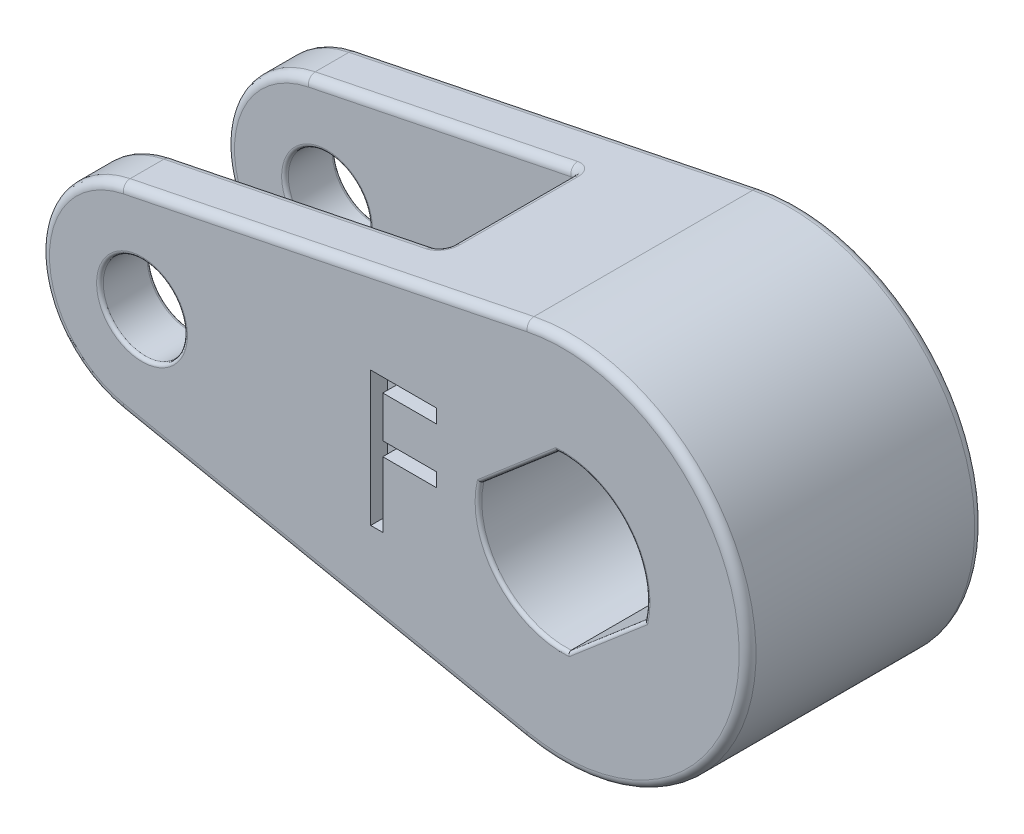
SolidWorks part; units mm, degrees
ref_plane "Front Plane" through (0, 0, 0) normal (0, 0, 1) x (1, 0, 0)
ref_plane "Top Plane" through (0, 0, 0) normal (0, 1, 0) x (1, 0, 0)
ref_plane "Right Plane" through (0, 0, 0) normal (1, 0, 0) x (0, 0, -1)
sketch "Sketch1" plane through (0, 0, 0) normal (0, 0, 1) x (1, 0, 0)
  line L0 (55, 0) -> (-55, 0) construction
  line L1 (-26.2, 5.8788) -> (-2.2, 10.7778)
  line L2 (-2.2, -10.7778) -> (-26.2, -5.8788)
  arc A0 (-2.2, 10.7778) -> (-2.2, -10.7778) centre (0, 0) cw
  arc A1 (-26.2, 5.8788) -> (-26.2, -5.8788) centre (-25, 0) ccw
  dimension "D1" = 11
  dimension "D2" = 6
  dimension "D3" = 25
extrude "Extrude1" add sketch "Sketch1" along normal blind 14
sketch "Sketch2" plane through (0, 0, 14) normal (0, 0, 1) x (1, 0, 0)
  line L0 (7.7, 0) -> (-7.7, 0) construction
  line L1 (-4.879, 1.0933) -> (-0.3166, 4.99)
  line L2 (4.879, -1.0933) -> (0.3166, -4.99)
  line L3 (0, 0) -> (-25, 0) construction
  arc A0 (-0.3166, 4.99) -> (4.879, -1.0933) centre (0, 0) cw
  circle A1 centre (-25, 0) radius 2.5
  arc A2 (-4.879, 1.0933) -> (0.3166, -4.99) centre (0, 0) ccw
  arc A4 (-26.2, 5.8788) -> (-26.2, -5.8788) centre (-25, 0) ccw construction
  dimension "D1" = 5
  dimension "D2" = 5
  dimension "D3" = 8
  dimension "D4" = 40.5
extrude "Cut-Extrude1" cut sketch "Sketch2" against normal through all
sketch "Sketch6" plane through (0, 0, 0) normal (1, 0, 0) x (0, 0, -1)
  line L1 (-11, 13) -> (-3, 13)
  line L2 (-11, 13) -> (-11, -13)
  line L3 (-11, -13) -> (-3, -13)
  line L4 (-3, 13) -> (-3, -13)
  dimension "D1" = 8
  dimension "D2" = 3
  dimension "D3" = 13
  dimension "D4" = 13
extrude "Cut-Extrude3" cut sketch "Sketch6" against normal through all from offset 10
ref_plane "Plane1" through (0, 0, 7) normal (0, 0, 1) x (1, 0, 0)
sketch "Sketch5" plane through (0, 0, 14) normal (0, 0, 1) x (1, 0, 0)
  line L0 (-25, 0) -> (0, 0) construction
  circle A0 centre (-25, 0) radius 2.5 construction
sketch "Sketch7" plane through (0, 0, 7) normal (0, 0, 1) x (1, 0, 0)
  circle A0 centre (-25, 0) radius 2.5 construction
  point P0 (-25, 0)
fillet "Fillet1" radius 0.5 18 edges at (-31, 0, 14) (-14.2, -8.3283, 14) (-10, -9.1856, 7) (-10, 0, 3) (-10, 9.1856, 7) (-10, 0, 11) (11, 0, 14) (-18.1, 7.5322, 11) (-31, 0, 11) (-18.1, -7.5322, 11) (-14.2, -8.3283, 0) (-31, 0, 3) (-18.1, 7.5322, 3) (-18.1, -7.5322, 3) (-31, 0, 0) (-14.2, 8.3283, 0) (11, 0, 0) (-14.2, 8.3283, 14)
fillet "Fillet2" radius 0.2 12 edges at (3.802, 3.2472, 0) (2.5978, -3.0416, 0) (-3.802, -3.2472, 0) (-2.5978, 3.0416, 0) (3.802, 3.2472, 14) (-2.5978, 3.0416, 14) (-3.802, -3.2472, 14) (2.5978, -3.0416, 14) (-22.5, 0, 0) (-22.5, 0, 14) (-25, -2.5, 11) (-25, 2.5, 3)
sketch "Sketch8" plane through (0, 0, 14) normal (0, 0, 1) x (1, 0, 0)
  text T0 "F" font "Century Gothic" height 8
extrude "Cut-Extrude4" cut sketch "Sketch8" against normal blind 1
sketch "Sketch9" plane through (0, 0, 0) normal (0, 0, -1) x (-1, 0, 0)
  text T0 "F" font "Century Gothic" height 8
extrude "Cut-Extrude5" cut sketch "Sketch9" against normal blind 1
